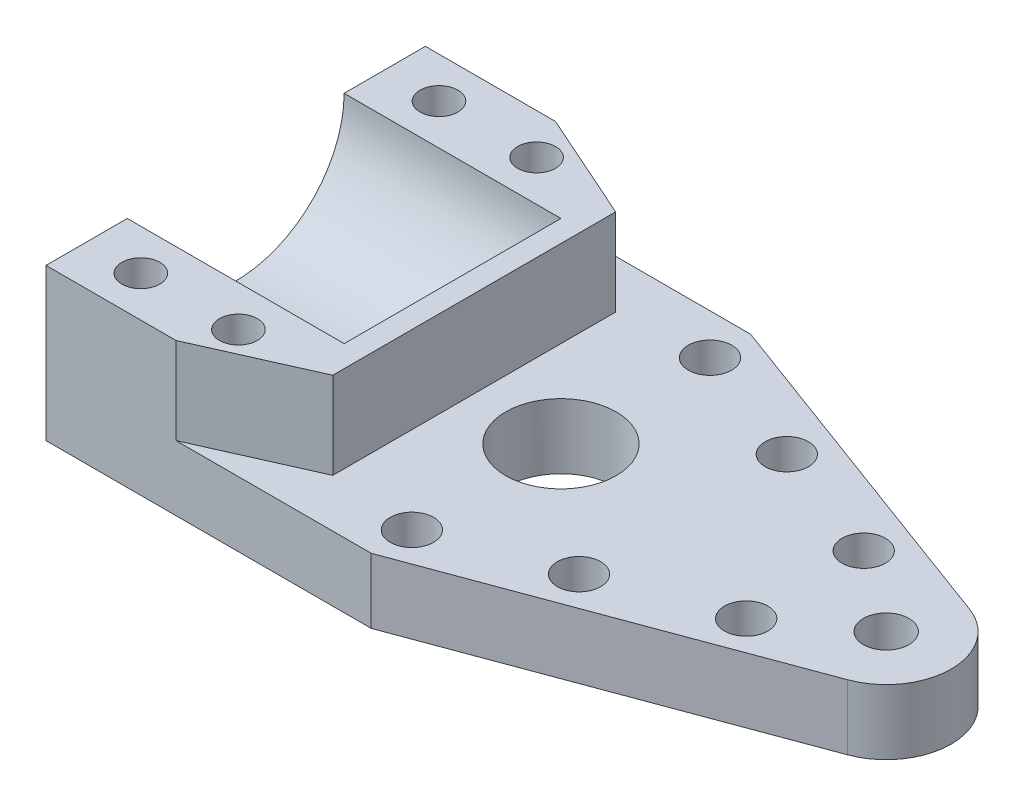
SolidWorks part; units mm, degrees
ref_plane "Front Plane" through (0, 0, 0) normal (0, 0, 1) x (1, 0, 0)
ref_plane "Top Plane" through (0, 0, 0) normal (0, 1, 0) x (1, 0, 0)
ref_plane "Right Plane" through (0, 0, 0) normal (1, 0, 0) x (0, 0, -1)
sketch "Sketch1" plane through (0, 0, 0) normal (0, 1, 0) x (1, 0, 0)
  line L0 (0, 0) -> (30, 0) construction
  line L1 (-30, -17.5) -> (30, -17.5)
  line L2 (-30, -17.5) -> (-30, 17.5)
  line L3 (-30, 17.5) -> (30, 17.5)
  line L4 (30, -17.5) -> (30, 17.5)
  line L5 (-30, -17.5) -> (30, 17.5) construction
  line L6 (-30, 17.5) -> (30, -17.5) construction
  line L7 (0, 17.5) -> (0, -17.5) construction
  line L8 (0, 17.5) -> (32.0824, 5.627)
  line L9 (0, -17.5) -> (32.0824, -5.627)
  circle A0 centre (0, 0) radius 5.1
  circle A1 centre (30, 0) radius 2.1
  circle A2 centre (30, 0) radius 6
  point P0 (0, 0)
  dimension "D1" = 10.2
  dimension "D5" = 4.2
  dimension "D6" = 12
  dimension "D2" = 60
  dimension "D3" = 35
  dimension "D4" = 30
extrude "Boss-Extrude1" add sketch "Sketch1" along normal blind 14 and the other way blind 14 contours A2 L4 L9 | L4 A2 A1 | A2 L8 L4 | A2 L4 L8 L3 L2 L1 L9 A0 | L4 A2 A1 region at (-29.3054, 0, 0) region at (30.5272, 0, 6.0827) region at (27.2225, 0, 0) region at (32.7775, 0, 0) region at (30.5272, 0, -6.0827)
sketch "Sketch2" plane through (-30, 0, 0) normal (-1, 0, 0) x (0, 0, 1)
  circle A0 centre (0, 0) radius 10
  dimension "D1" = 20
extrude "Cut-Extrude1" cut sketch "Sketch2" against normal blind 20 contours A0
sketch "Sketch3" plane through (-30, 0, 0) normal (-1, 0, 0) x (0, 0, 1)
  line L0 (-28.7806, 0) -> (30.768, 0)
  line L1 (30.768, 0) -> (25.7627, 25.9835)
  line L2 (25.7627, 25.9835) -> (-26.2043, 26.646)
  line L3 (-26.2043, 26.646) -> (-28.7806, 0)
extrude "Cut-Extrude2" cut sketch "Sketch3" against normal blind 98
sketch "Sketch4" plane through (0, 0, 0) normal (0, 1, 0) x (1, 0, 0)
  line L0 (-30, 13.75) -> (0, 13.75) construction
  line L1 (-30, 17.5) -> (-30, 10) construction
  line L2 (0, 13.75) -> (0, -13.75) construction
  line L3 (0, -13.75) -> (-30, -13.75) construction
  line L4 (-30, -10) -> (-30, -17.5) construction
  line L5 (-32.6009, 0) -> (37.1544, 0) construction
  line L6 (0, 13.75) -> (37.1544, 0) construction
  line L7 (37.1544, 0) -> (0, -13.75) construction
  line L8 (0, 17.5) -> (32.0824, 5.627) construction
  line L9 (0, -17.5) -> (32.0824, -5.627) construction
  circle A0 centre (0, 13.75) radius 2
  circle A1 centre (-25, 13.75) radius 1.75
  circle A2 centre (-16, 13.75) radius 1.75
  circle A4 centre (-16, -13.75) radius 1.75
  circle A5 centre (-25, -13.75) radius 1.75
  circle A19 centre (11.2541, 9.5851) radius 2
  circle A20 centre (22.5081, 5.4203) radius 2
  circle A23 centre (22.5081, -5.4203) radius 2
  circle A24 centre (11.2541, -9.5851) radius 2
  circle A25 centre (0, -13.75) radius 2
  dimension "D4" = 3.5
  dimension "D5" = 4
  dimension "D1" = 5
  dimension "D2" = 9
  dimension "D3" = 3
extrude "Cut-Extrude3" cut sketch "Sketch4" against normal blind 98
sketch "Sketch5" plane through (0, 0, 0) normal (0, 1, 0) x (1, 0, 0)
  line L0 (-8, 24.0497) -> (-8, -23.9632)
  line L1 (-8, 24.0497) -> (56.9644, 12.8899)
  line L2 (56.9644, 12.8899) -> (49.9553, -27.9126)
  line L3 (49.9553, -27.9126) -> (-8, -23.9632)
  dimension "D1" = 8
extrude "Cut-Extrude4" cut sketch "Sketch5" against normal blind 8
chamfer "Chamfer2" distance 10 angle 24 2 edges at (-8, -4, 17.5) (-8, -4, -17.5) first distance on face at (-12.6667, -7.3333, 17.5) first distance on face at (-12.6667, -7.3333, -17.5)
sketch "Sketch6" plane through (0, -14, 0) normal (0, -1, 0) x (1, 0, 0)
  circle A0 centre (-25, 13.75) radius 3.25
  circle A1 centre (-16, 13.75) radius 3.25
  circle A2 centre (-25, -13.75) radius 3.25
  circle A3 centre (-16, -13.75) radius 3.25
  dimension "D1" = 6.5
extrude "Cut-Extrude5" cut sketch "Sketch6" against normal blind 1.5
